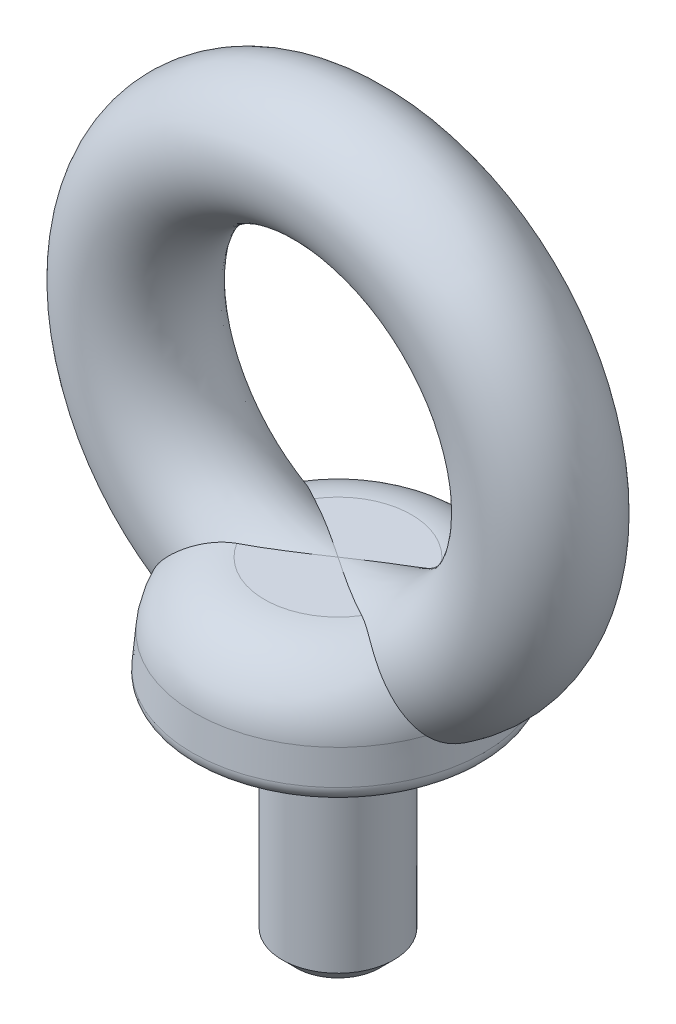
SolidWorks part; units mm, degrees
material "普通碳钢"
ref_plane "前视基准面" through (0, 0, 0) normal (0, 0, 1) x (1, 0, 0)
ref_plane "上视基准面" through (0, 0, 0) normal (0, 1, 0) x (1, 0, 0)
ref_plane "右视基准面" through (0, 0, 0) normal (1, 0, 0) x (0, 0, -1)
sketch "草图1" plane through (0, 0, 0) normal (0, 1, 0) x (1, 0, 0)
  circle A0 centre (0, 0) radius 10.55
extrude "拉伸1" add sketch "草图1" along normal blind 8 draft 5
fillet "圆角1" radius 5 1 edges at (0, 8, 9.8501)
sketch "草图2" plane through (0, 0, 0) normal (0, 0, 1) x (1, 0, 0)
  circle A0 centre (0, 18) radius 14.5
sketch "草图3" plane through (0, 0, 0) normal (1, 0, 0) x (0, 0, -1)
  line L0 (0, 32.5) -> (0, 3.5) construction
  circle A0 centre (0, 32.5) radius 4.5
sweep "扫描1" add profiles "草图3" path "草图2"
sketch "草图4" plane through (0, 0, 0) normal (0, 0, 1) x (1, 0, 0)
  line L0 (0, 0) -> (10.55, 0)
  line L1 (-10.55, 0) -> (10.55, 0) construction
  line L2 (10.55, 0) -> (10.55, -2.4025)
  line L3 (10.55, -2.4025) -> (-10.55, -2.4025)
  line L4 (-10.55, -2.4025) -> (-10.55, 0)
  line L5 (-10.55, 0) -> (0, 0)
extrude "切除-拉伸1" cut sketch "草图4" against normal blind 8 and the other way blind 8
sketch "草图5" plane through (0, 0, 0) normal (0, -1, 0) x (1, 0, 0)
  circle A0 centre (0, 0) radius 3
extrude "拉伸2" add sketch "草图5" along normal blind 2
sketch "草图6" plane through (0, -2, 0) normal (0, -1, 0) x (1, 0, 0)
  circle A0 centre (0, 0) radius 4
extrude "拉伸3" add sketch "草图6" along normal blind 14
fillet "圆角2" radius 1 2 edges at (0, 0, 10.55) (0, 0, 3)
chamfer "倒角1" distance 1 angle 45 2 edges at (0, -16, -4) (0, -2, -4)
scale "缩放比例1" scale about origin uniform scaling yes scale factor 0.25
